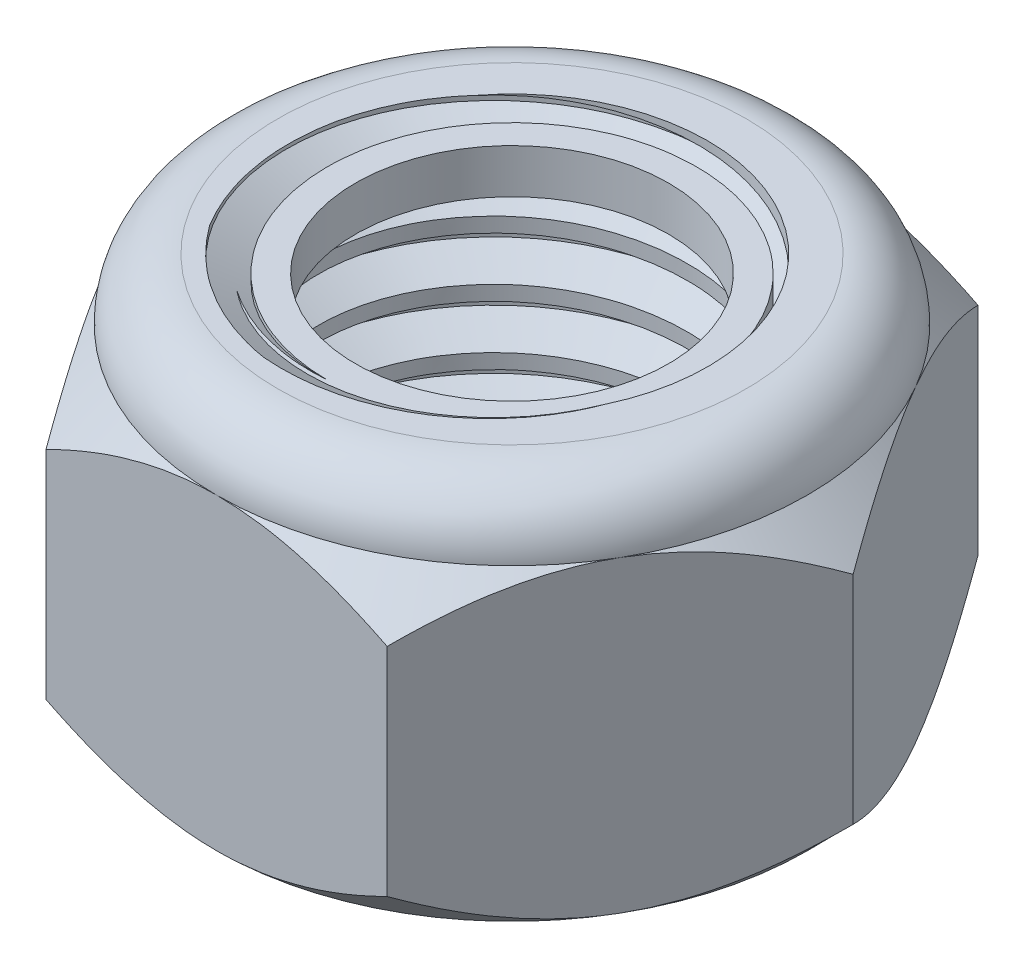
SolidWorks part; units mm, degrees
material "AISI 1045 Steel, cold drawn"
ref_plane "Front Plane" through (0, 0, 0) normal (0, 0, 1) x (1, 0, 0)
ref_plane "Top Plane" through (0, 0, 0) normal (0, 1, 0) x (1, 0, 0)
ref_plane "Right Plane" through (0, 0, 0) normal (1, 0, 0) x (0, 0, -1)
sketch "Sketch1" plane through (0, 0, 0) normal (0, 1, 0) x (1, 0, 0)
  line L1 (2.3094, -4) -> (4.6188, 0)
  line L2 (4.6188, 0) -> (2.3094, 4)
  line L3 (2.3094, 4) -> (-2.3094, 4)
  line L4 (-2.3094, 4) -> (-4.6188, 0)
  line L5 (-4.6188, 0) -> (-2.3094, -4)
  line L6 (-2.3094, -4) -> (2.3094, -4)
  circle A0 centre (0, 0) radius 4 construction
  dimension "D1" = 8
extrude "Boss-Extrude1" add sketch "Sketch1" along normal mid plane 4.17
sketch "Sketch2" plane through (0, 2.085, 0) normal (0, 1, 0) x (1, 0, 0)
  circle A0 centre (0, 0) radius 4
  dimension "D1" = 8
extrude "Cut-Extrude1" cut sketch "Sketch2" against normal through all draft 45 flip side to cut
mirror "Mirror1" about plane through (0, 0, 0) normal (0, 1, 0) of "Cut-Extrude1"
sketch "Sketch3" plane through (0, 0, 0) normal (1, 0, 0) x (0, 0, -1)
  line L0 (-2, 2.085) -> (-4, 2.085) construction
  line L1 (0, 2.085) -> (0, 2.915)
  line L2 (2, 2.085) -> (-2, 2.085) construction
  line L3 (-3.17, 2.915) -> (0, 2.915)
  line L4 (-4, 2.085) -> (0, 2.085)
  arc A0 (-3.17, 2.915) -> (-4, 2.085) centre (-3.17, 2.085) ccw
  dimension "D1" = 1.66
revolve "Revolve1" add sketch "Sketch3" angle 360 about L1
sketch "Sketch4" plane through (0, 0, 0) normal (1, 0, 0) x (0, 0, -1)
  line L0 (0, 0) -> (0, 2.915)
  line L1 (3.17, 2.915) -> (-3.17, 2.915) construction
  line L2 (0, 2.915) -> (2.65, 2.915)
  line L3 (2.65, 2.915) -> (2.65, 2.685)
  line L4 (2.65, 2.685) -> (2.12, 2.685)
  line L5 (2.12, 2.685) -> (2.12, 2.085)
  line L6 (2, 2.085) -> (4, 2.085) construction
  line L7 (2.12, 2.085) -> (2.5, 2.085)
  line L8 (2.5, 2.085) -> (2.5, -2.085)
  line L9 (2, -2.085) -> (4, -2.085) construction
  line L10 (2.5, -2.085) -> (0, -2.085)
  line L11 (-2, -2.085) -> (2, -2.085) construction
  line L12 (0, -2.085) -> (0, 0)
  dimension "D1" = 2.65
  dimension "D2" = 0.23
  dimension "D3" = 0.53
  dimension "D4" = 0.38
revolve "Cut-Revolve1" cut sketch "Sketch4" angle 360 about L0
thread "Thread1" pitch 0.8 method cut profile "Thread Profile3" start angle 0, offset 5, length 10, pitch 0.8, diameter 5
ref_plane "Plane3" through (-2.5, 7.085, 0) normal (0, 0, 1) x (-1, 0, 0)
sketch "Thread Profile3" plane through (-2.5, 7.085, 0) normal (0, 0, 1) x (-1, 0, 0)
  line L0 (0, 0) -> (0, 0.8) construction
  line L1 (0, 0) -> (0.433, 0.25)
  line L2 (0.433, 0.25) -> (0.433, 0.35)
  line L3 (0.433, 0.35) -> (0, 0.6)
  line L4 (0.433, 0.3) -> (0, 0.3) construction
  line L11 (0, 0) -> (0, 0.6)
  point P2 (0, 0)
  dimension "Pitch" = 0.8
  dimension "Profile_Angle" = 60
  dimension "Profile_Land" = 0.1
  dimension "Profile_Height" = 0.433
